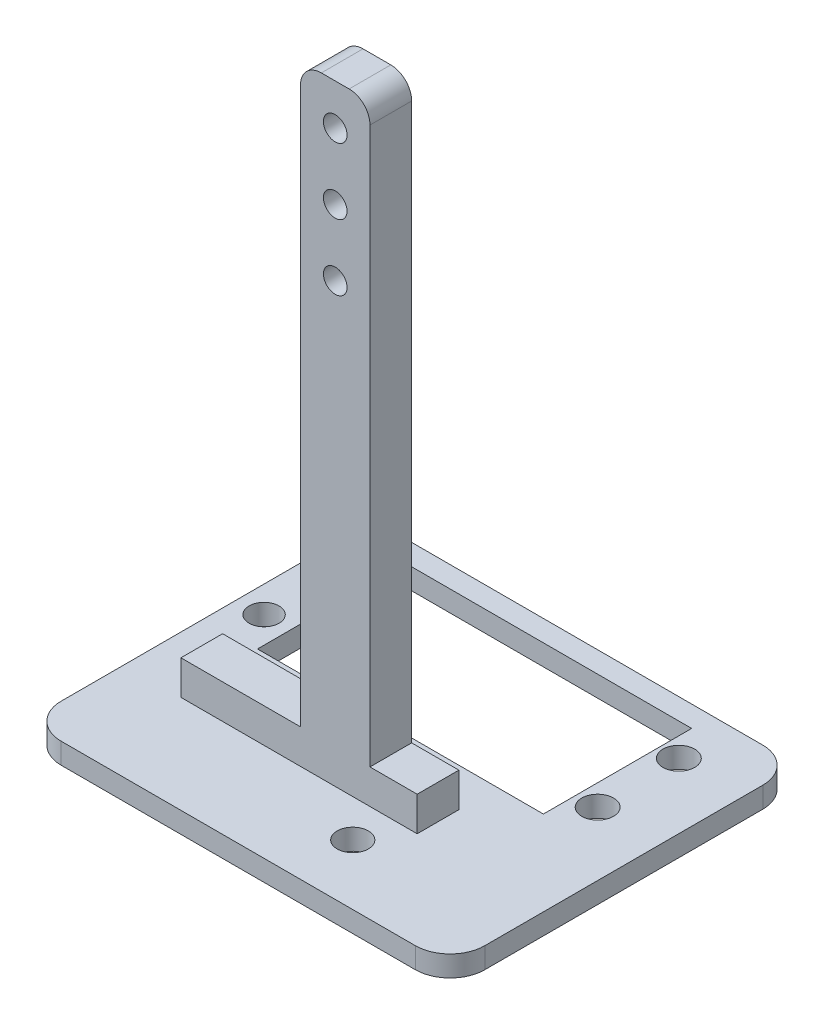
SolidWorks part; units mm, degrees
ref_plane "Front Plane" through (0, 0, 0) normal (0, 0, 1) x (1, 0, 0)
ref_plane "Top Plane" through (0, 0, 0) normal (0, 1, 0) x (1, 0, 0)
ref_plane "Right Plane" through (0, 0, 0) normal (1, 0, 0) x (0, 0, -1)
sketch "Sketch1" plane through (0, 0, 0) normal (0, 0, 1) x (1, 0, 0)
  line L0 (-20.3006, -42.2195) -> (-37.507, -42.2195)
  line L1 (-17.3006, 40.7805) -> (-13.3006, 40.7805)
  line L2 (-20.3006, 37.7805) -> (-20.3006, -42.2195)
  line L4 (-10.3006, 37.7805) -> (-10.3006, -42.2195)
  line L30 (-10.3006, -42.2195) -> (-3.507, -42.2195)
  line L31 (-3.507, -42.2195) -> (-3.507, -47.1537)
  line L32 (-3.507, -47.1537) -> (-7.507, -47.1537)
  line L33 (-7.507, -47.1537) -> (-7.507, -50.1537)
  line L34 (-7.507, -50.1537) -> (-12.507, -50.1537)
  line L35 (-12.507, -50.1537) -> (-12.507, -47.1537)
  line L36 (-12.507, -47.1537) -> (-16.507, -47.1537)
  line L37 (-16.507, -47.1537) -> (-16.507, -50.1537)
  line L38 (-16.507, -50.1537) -> (-21.507, -50.1537)
  line L39 (-21.507, -50.1537) -> (-21.507, -47.1537)
  line L40 (-21.507, -47.1537) -> (-25.507, -47.1537)
  line L41 (-25.507, -47.1537) -> (-25.507, -50.1537)
  line L42 (-25.507, -50.1537) -> (-30.507, -50.1537)
  line L43 (-30.507, -50.1537) -> (-30.507, -47.1537)
  line L44 (-30.507, -47.1537) -> (-37.507, -47.1537)
  line L45 (-37.507, -47.1537) -> (-37.507, -42.2195)
  circle A0 centre (-15.3006, 25.3805) radius 1.7
  circle A1 centre (-15.3006, 15.8805) radius 1.7
  circle A2 centre (-15.3006, 34.8805) radius 1.7
  arc A3 (-17.3006, 40.7805) -> (-20.3006, 37.7805) centre (-17.3006, 37.7805) ccw
  arc A4 (-13.3006, 40.7805) -> (-10.3006, 37.7805) centre (-13.3006, 37.7805) cw
  point P14 (-15.3006, 40.7805)
  dimension "D1" = 3.4
  dimension "D4" = 3
  dimension "D2" = 9.5
  dimension "D3" = 9.5
  dimension "D5" = 80
  dimension "D6" = 10
  dimension "D7" = 5.9
extrude "Boss-Extrude1" add sketch "Sketch1" along normal blind 6
sketch "Sketch3" plane through (0, -47.1537, 0) normal (0, -1, 0) x (1, 0, 0)
  line L1 (10.3059, -29.9226) -> (-40.6541, -29.9226)
  line L2 (15.3059, -24.9226) -> (15.3059, 15.0774)
  line L3 (10.3059, 20.0774) -> (-40.6541, 20.0774)
  line L4 (-45.6541, -24.9226) -> (-45.6541, 15.0774)
  line L18 (-30.507, 6) -> (-25.507, 6)
  line L19 (-30.507, 6) -> (-30.507, 0)
  line L20 (-30.507, 0) -> (-25.507, 0)
  line L21 (-25.507, 6) -> (-25.507, 0)
  line L22 (-21.507, 6) -> (-16.507, 6)
  line L23 (-21.507, 6) -> (-21.507, 0)
  line L24 (-21.507, 0) -> (-16.507, 0)
  line L25 (-16.507, 6) -> (-16.507, 0)
  line L26 (-12.507, 6) -> (-7.507, 6)
  line L27 (-12.507, 6) -> (-12.507, 0)
  line L28 (-12.507, 0) -> (-7.507, 0)
  line L29 (-7.507, 6) -> (-7.507, 0)
  circle A3 centre (-7.3751, 11.4) radius 2.25
  arc A4 (10.3059, -29.9226) -> (15.3059, -24.9226) centre (10.3059, -24.9226) ccw
  arc A5 (15.3059, 15.0774) -> (10.3059, 20.0774) centre (10.3059, 15.0774) ccw
  arc A6 (-40.6541, 20.0774) -> (-45.6541, 15.0774) centre (-40.6541, 15.0774) ccw
  arc A7 (-40.6541, -29.9226) -> (-45.6541, -24.9226) centre (-40.6541, -24.9226) cw
  point P16 (0, 0)
  point P21 (-7.507, 3)
  dimension "D2" = 50
  dimension "D5" = 8.4
  dimension "D6" = 4.5
  dimension "D7" = 5
  dimension "D1" = 60.96
extrude "Boss-Extrude2" add sketch "Sketch3" along normal blind 3 separate body
sketch "Sketch4" plane through (0, -47.1537, 0) normal (0, 1, 0) x (1, 0, 0)
  line L1 (3.1139, 26.8823) -> (-38.0341, 26.8823)
  line L2 (3.1139, 26.8823) -> (3.1139, 5.5463)
  line L3 (3.1139, 5.5463) -> (-38.0341, 5.5463)
  line L4 (-38.0341, 26.8823) -> (-38.0341, 5.5463)
  line L6 (-45.6541, -15.0774) -> (-45.6541, 24.9226) construction
  dimension "D1" = 41.148
  dimension "D2" = 21.336
  dimension "D3" = 7.62
extrude "Cut-Extrude1" cut sketch "Sketch4" against normal blind 7.62
sketch "Sketch5" plane through (0, -47.1537, 0) normal (0, 1, 0) x (1, 0, 0)
  line L1 (3.1139, 5.5463) -> (3.1139, 26.8823) construction
  circle A0 centre (-41.8441, 22.2426) radius 2.286
  circle A1 centre (-41.8441, 10.3046) radius 2.159
  circle A2 centre (5.9079, 22.2426) radius 2.286
  circle A3 centre (6.1619, 10.3046) radius 2.286
  dimension "D1" = 11.938
  dimension "D3" = 4.572
  dimension "D5" = 4.572
  dimension "D2" = 47.752
  dimension "D6" = 3.048
extrude "Cut-Extrude2" cut sketch "Sketch5" against normal through all
